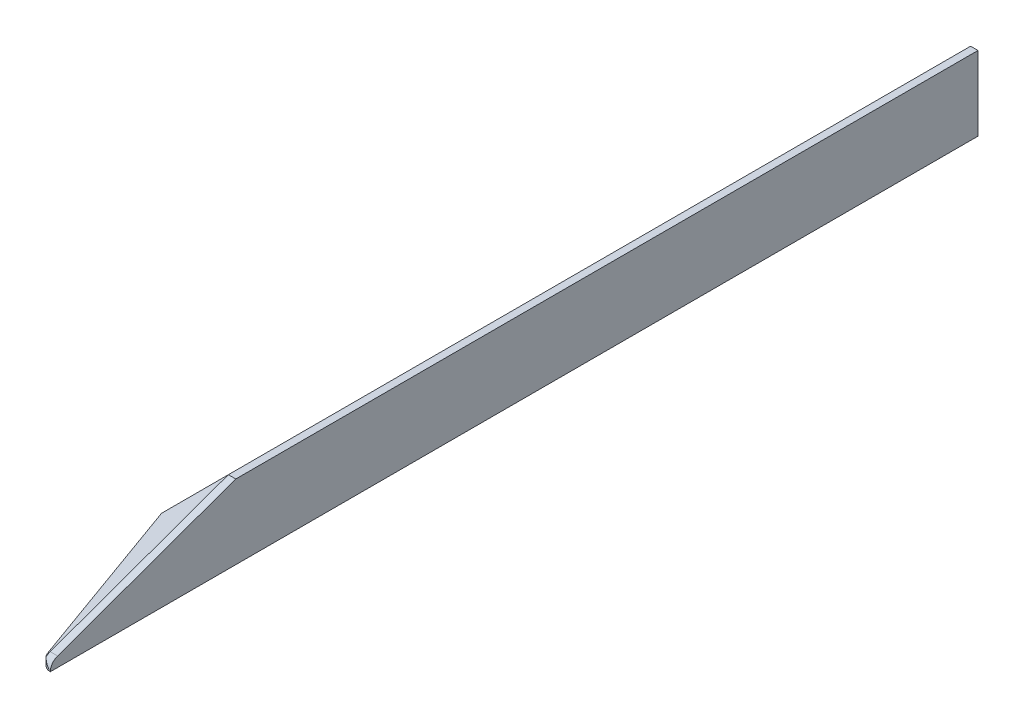
SolidWorks part; units mm, degrees
ref_plane "前视基准面" through (0, 0, 0) normal (0, 0, 1) x (1, 0, 0)
ref_plane "上视基准面" through (0, 0, 0) normal (0, 1, 0) x (1, 0, 0)
ref_plane "右视基准面" through (0, 0, 0) normal (1, 0, 0) x (0, 0, -1)
sketch "草图1" plane through (0, 0, 0) normal (0, 0, 1) x (1, 0, 0)
  line L0 (-20, 0) -> (0, 0)
  line L1 (0, 0) -> (0, 20)
  line L2 (-20, 0) -> (-20, 2)
  line L3 (-20, 2) -> (-2, 2)
  line L4 (-2, 2) -> (-2, 20)
  line L5 (-2, 20) -> (0, 20)
  dimension "D1" = 20
  dimension "D2" = 20
  dimension "D3" = 2
extrude "凸台-拉伸1" add sketch "草图1" along normal blind 250
sketch "草图2" plane through (-2, 0, 0) normal (-1, 0, 0) x (0, 0, 1)
  line L0 (250, 2) -> (200, 20)
  line L1 (250, 20) -> (0, 20) construction
  line L2 (200, 20) -> (250, 20)
  line L3 (250, 20) -> (250, 2)
  dimension "D1" = 50
extrude "切除-拉伸1" cut sketch "草图2" against normal blind 10
sketch "草图3" plane through (0, 2, 0) normal (0, 1, 0) x (1, 0, 0)
  line L0 (-2, -250) -> (-20, -200)
  line L1 (-20, -250) -> (-20, 0) construction
  line L2 (-20, -200) -> (-20, -250)
  line L3 (-20, -250) -> (-2, -250)
extrude "切除-拉伸2" cut sketch "草图3" against normal blind 10
fillet "圆角1" radius 3 2 edges at (-1, 2, 250) (-2, 1, 250)
sketch "草图4" plane through (0, 0, 0) normal (1, 0, 0) x (0, 0, -1)
  line L0 (-250, 0) -> (0, 0) construction
  line L1 (0, 0) -> (0, 20) construction
  circle A0 centre (-6, 12) radius 2.5
  circle A1 centre (-14, 12) radius 2.5
  dimension "D1" = 5
  dimension "D4" = 8
  dimension "D2" = 12
  dimension "D3" = 6
sketch "草图5" plane through (0, 0, 0) normal (0, -1, 0) x (1, 0, 0)
  line L0 (-20, 0) -> (0, 0) construction
  line L2 (0, 3.5) -> (0, 8.5) construction
  line L3 (-20, 200) -> (-20, 0) construction
  circle A0 centre (-14, 7.5) radius 2.05
  circle A1 centre (-6, 7.5) radius 2.05
  dimension "D1" = 4.1
  dimension "D4" = 6
  dimension "D2" = 7.5
  dimension "D3" = 6
extrude "切除-拉伸4" cut sketch "草图5" against normal blind 10
